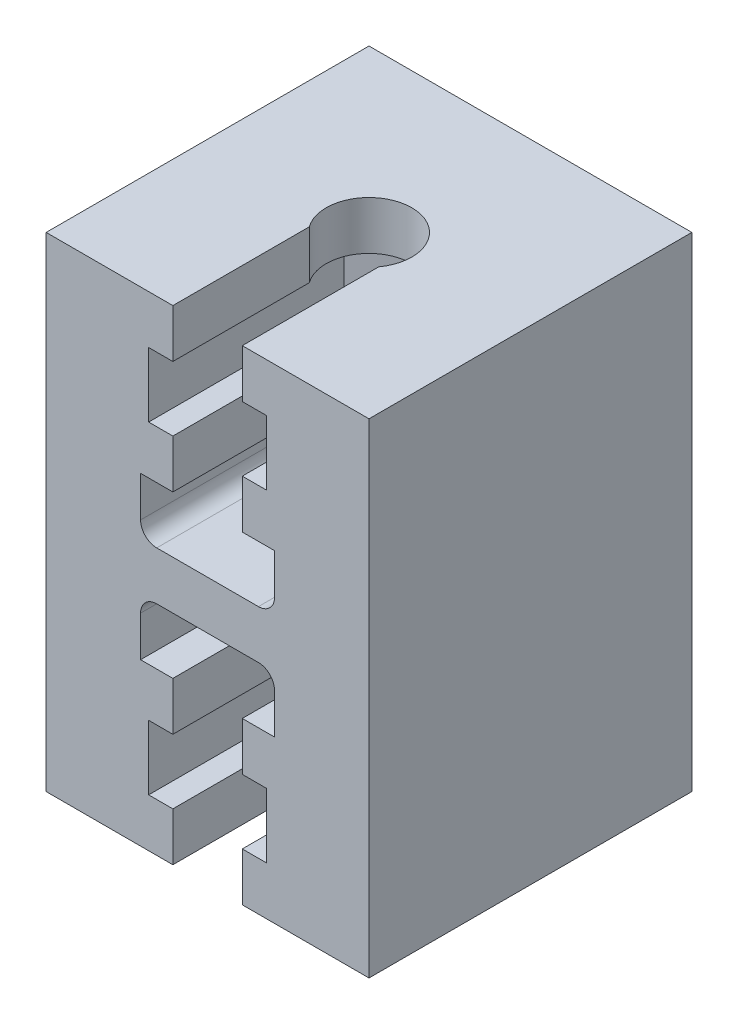
SolidWorks part; units mm, degrees
ref_plane "Front Plane" through (0, 0, 0) normal (0, 0, 1) x (1, 0, 0)
ref_plane "Top Plane" through (0, 0, 0) normal (0, 1, 0) x (1, 0, 0)
ref_plane "Right Plane" through (0, 0, 0) normal (1, 0, 0) x (0, 0, -1)
sketch "Sketch1" plane through (0, 0, 0) normal (0, 0, 1) x (1, 0, 0)
  line L1 (-10, -15) -> (10, -15)
  line L2 (-10, -15) -> (-10, 15)
  line L3 (-10, 15) -> (10, 15)
  line L4 (10, -15) -> (10, 15)
  line L5 (0, 15) -> (0, -15) construction
  line L6 (-10, 0) -> (10, 0) construction
  point P0 (0, 0)
  dimension "D1" = 20
  dimension "D2" = 30
extrude "Boss-Extrude1" add sketch "Sketch1" along normal blind 10 and the other way blind 10
sketch "Sketch2" plane through (0, 0, 0) normal (0, 0, 1) x (1, 0, 0)
  line L0 (0, 15) -> (0, -15) construction
  line L1 (10, 15) -> (-10, 15) construction
  line L2 (-10, -15) -> (10, -15) construction
  line L3 (0, -15) -> (2.15, -15)
  line L4 (-2.15, -15) -> (2.15, -15) construction
  line L5 (-2.15, -15) -> (-2.15, -5) construction
  line L6 (-2.15, -5) -> (2.15, -5) construction
  line L7 (2.15, -15) -> (2.15, -5) construction
  line L8 (0, -5) -> (0, -15) construction
  line L9 (-2.15, -10) -> (2.15, -10) construction
  line L10 (2.15, -15) -> (2.15, -5)
  line L11 (2.15, -5) -> (4.15, -5)
  line L12 (0, -1.5) -> (10, -1.5) construction
  line L13 (10, -15) -> (10, 15) construction
  line L14 (4.15, -3.2222) -> (4.15, -6.7778) construction
  line L15 (-2.9035, -1.5) -> (2.9067, -1.5) construction
  line L16 (0, -15) -> (0, -1.5)
  spline S0 degree 3 poles (4.15, -5) (4.15, -2.6318) (2.4702, -1.5) (0, -1.5) knots 0 0 0 0 1 1 1 1
  point P19 (0, 0)
  point P714 (0, -10)
  dimension "D1" = 4.3
  dimension "D2" = 10
  dimension "D3" = 8.3
  dimension "D4" = 3.5
revolve "Cut-Revolve1" cut sketch "Sketch2" angle 360 about L0
sketch "Sketch3" plane through (0, 15, 0) normal (0, 1, 0) x (1, 0, 0)
  circle A0 centre (0, 0) radius 2.65
  dimension "D1" = 5.3
extrude "Cut-Extrude1" cut sketch "Sketch3" against normal through all
sketch "Sketch4" plane through (0, 0, 0) normal (0, 0, 1) x (1, 0, 0)
  line L0 (0, 15) -> (0, -15) construction
  line L3 (-2.15, -15) -> (2.15, -15)
  line L4 (-2.15, -15) -> (2.15, -15) construction
  line L5 (-2.15, -15) -> (-2.15, -5) construction
  line L6 (-2.15, -5) -> (2.15, -5) construction
  line L7 (2.15, -15) -> (2.15, -5) construction
  line L8 (0, -5) -> (0, -15) construction
  line L9 (-2.15, -10) -> (2.15, -10) construction
  line L10 (2.15, -15) -> (2.15, -5)
  line L11 (2.15, -5) -> (4.15, -5)
  line L12 (4.15, -5) -> (4.15, -2.5)
  line L14 (3.15, -1.5) -> (0, -1.5)
  line L15 (0, -1.5) -> (-3.15, -1.5)
  line L17 (-10, -15) -> (10, -15) construction
  line L18 (-2.15, -5) -> (-4.15, -5)
  line L19 (-2.15, -15) -> (-2.15, -5)
  line L20 (-4.15, -2.5) -> (-4.15, -5)
  arc A0 (-3.15, -1.5) -> (-4.15, -2.5) centre (-3.15, -2.5) ccw
  arc A1 (4.15, -2.5) -> (3.15, -1.5) centre (3.15, -2.5) ccw
  point P714 (0, -10)
  dimension "D5" = 1
  dimension "D1" = 4.3
  dimension "D2" = 10
  dimension "D3" = 8.3
  dimension "D4" = 3.5
extrude "Cut-Extrude2" cut sketch "Sketch4" along normal through all
ref_plane "Plane1" through (0, -10, 0) normal (0, -1, 0) x (-1, 0, 0)
sketch "Sketch5" plane through (0, -10, 0) normal (0, -1, 0) x (-1, 0, 0)
  line L0 (-3.65, -2.1073) -> (-3.65, -10)
  line L1 (3.65, -2.1073) -> (3.65, 2.1073)
  line L2 (3.65, 2.1073) -> (0, 4.2147)
  line L3 (0, 4.2147) -> (-3.65, 2.1073)
  line L4 (-3.65, 2.1073) -> (-3.65, -2.1073)
  line L5 (-3.65, -2.1073) -> (0, -4.2147) construction
  line L6 (0, -4.2147) -> (3.65, -2.1073) construction
  line L7 (-2.15, -10) -> (-10, -10) construction
  line L8 (-3.65, -10) -> (3.65, -10)
  line L9 (10, -10) -> (2.15, -10) construction
  line L10 (3.65, -10) -> (3.65, -2.1073)
  circle A0 centre (0, 0) radius 3.65 construction
  dimension "D1" = 7.3
extrude "Cut-Extrude3" cut sketch "Sketch5" against normal blind 2 and the other way blind 2
mirror "Mirror1" about plane through (0, 0, 0) normal (0, 1, 0) of "Cut-Extrude2", "Cut-Extrude3"
equation "\"D1@Cut-Extrude3\"=3.5/2"
equation "\"D2@Cut-Extrude3\"=3.5/2"
